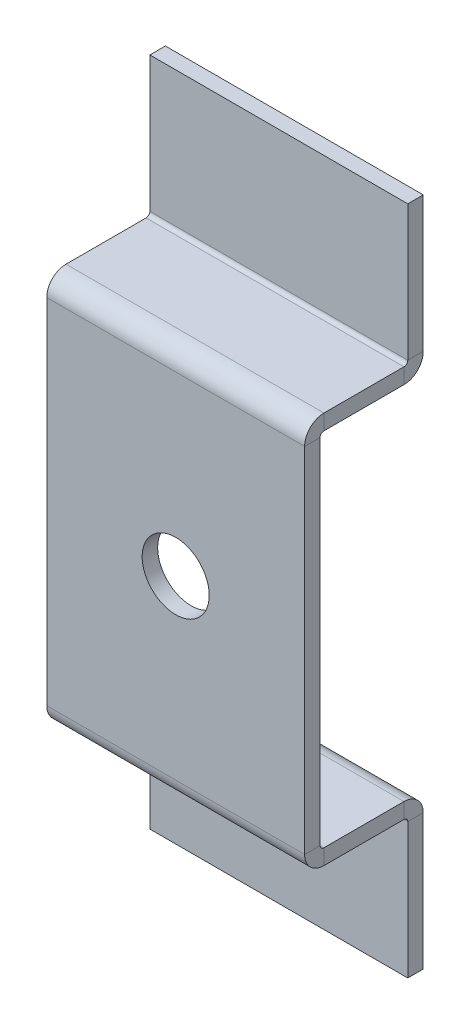
SolidWorks part; units mm, degrees
note: The reader was unsure of these and kept them because the rebuilt part matched: flange length of "边线-法兰1", "边线-法兰2".
ref_plane "前视基准面" through (0, 0, 0) normal (0, 0, 1) x (1, 0, 0)
ref_plane "上视基准面" through (0, 0, 0) normal (0, 1, 0) x (1, 0, 0)
ref_plane "右视基准面" through (0, 0, 0) normal (1, 0, 0) x (0, 0, -1)
other "Configuration Table"
sketch "草图1" plane through (0, 0, 0) normal (0, 0, 1) x (1, 0, 0)
  line L1 (0, 0) -> (50, 0)
  line L2 (0, 0) -> (0, 70)
  line L3 (0, 70) -> (50, 70)
  line L4 (50, 0) -> (50, 70)
  dimension "D1" = 70
  dimension "D2" = 50
base flange "基体-法兰1" sketch "草图1" thickness 3 reverse thickness direction no parameters "D1"=0.7366
edge flange "边线-法兰1" sketch "草图10" flange profiles "草图10", "草图11" flange angle 90 flange length 20 flange position material outside bend radius 0.7366 thickness 3 relief rectangular parameters "D6"=10, "D8"=1
sketch "草图10" plane through (0, 70, -3) normal (0, -1, 0) x (-1, 0, 0)
  line L2 (-50, 0) -> (-50, 17)
  line L3 (-50, 17) -> (0, 17)
  line L4 (0, 17) -> (0, 0)
  line L5 (0, 0) -> (-50, 0) construction
  line L6 (0, 0) -> (-50, 0)
sketch "草图11" plane through (0, 0, -3) normal (0, 1, 0) x (1, 0, 0)
  line L0 (50, 0) -> (0, 0) construction
  line L1 (50, 0) -> (0, 0)
  line L2 (50, 0) -> (50, 17)
  line L3 (50, 17) -> (0, 17)
  line L4 (0, 17) -> (0, 0)
bend "边线折弯1" bend radius 0.7366 bend angle 90 parameters "D5"=1
bend "边线折弯2" bend radius 0.7366 bend angle 90 parameters "D5"=2
edge flange "边线-法兰2" sketch "草图16" flange profiles "草图16", "草图17" flange angle 90 flange length 30 flange position material outside bend radius 0.7366 thickness 3 relief rectangular parameters "D6"=10, "D8"=1
sketch "草图16" plane through (0, -3, -20) normal (0, 0, -1) x (1, 0, 0)
  line L2 (0, 0) -> (0, 27)
  line L3 (0, 27) -> (50, 27)
  line L4 (50, 27) -> (50, 0)
  line L7 (50, 0) -> (0, 0) construction
  line L8 (50, 0) -> (0, 0)
sketch "草图17" plane through (0, 73, -20) normal (0, 0, -1) x (-1, 0, 0)
  line L0 (0, 0) -> (-50, 0) construction
  line L1 (0, 0) -> (-50, 0)
  line L2 (-50, 0) -> (-50, 27)
  line L3 (-50, 27) -> (0, 27)
  line L4 (0, 27) -> (0, 0)
bend "边线折弯3" bend radius 0.7366 bend angle 90 parameters "D5"=3
bend "边线折弯4" bend radius 0.7366 bend angle 90 parameters "D5"=4
sketch "草图18" plane through (0, 0, 0) normal (0, 0, 1) x (1, 0, 0)
  line L7 (50, -30) -> (0, -30) construction
  line L8 (50, 0.7366) -> (50, 69.2634) construction
  circle A0 centre (25, 35) radius 6.5
  dimension "D5" = 13
  dimension "D3" = 65
  dimension "D4" = 25
extrude "切除-拉伸1" cut sketch "草图18" against normal through all normal cut yes
sketch "折弯-线1" plane through (0, 0, 0) normal (0, 1, 0) x (1, 0, 0)
sketch "边界框1" plane through (0, 0, 0) normal (0, 1, 0) x (1, 0, 0)
sheet metal parameters "钣金6" thickness 3 parameters "D1"=0.7366
flat pattern "平板型式6" [suppressed]
sketch "折弯-线2" plane through (0, 0, 0) normal (0, 1, 0) x (1, 0, 0)
sketch "边界框2" [suppressed] plane through (0, 0, 0) normal (0, 1, 0) x (1, 0, 0)
sheet metal parameters "钣金7" thickness 3 parameters "D1"=0.7366
flat pattern "平板型式6" [suppressed]
sketch "折弯-线2" plane through (0, 0, 0) normal (0, 1, 0) x (1, 0, 0)
sketch "边界框2" [suppressed] plane through (0, 0, 0) normal (0, 1, 0) x (1, 0, 0)
bend of the flat pattern "展平-<边线折弯1>1"
bend of the flat pattern "展平-<边线折弯2>1"
sheet metal parameters "钣金8" thickness 3 parameters "D1"=0.7366
flat pattern "平板型式6" [suppressed]
sketch "折弯-线2" plane through (0, 0, 0) normal (0, 1, 0) x (1, 0, 0)
sketch "边界框2" [suppressed] plane through (0, 0, 0) normal (0, 1, 0) x (1, 0, 0)
bend of the flat pattern "展平-<边线折弯1>1"
bend of the flat pattern "展平-<边线折弯2>1"
bend of the flat pattern "展平-<边线折弯3>1"
bend of the flat pattern "展平-<边线折弯4>1"
sheet metal parameters "钣金9" thickness 3 parameters "D1"=0.7366
flat pattern "平板型式6" [suppressed]
sketch "折弯-线2" plane through (0, 0, 0) normal (0, 1, 0) x (1, 0, 0)
sketch "边界框2" [suppressed] plane through (0, 0, 0) normal (0, 1, 0) x (1, 0, 0)
bend of the flat pattern "展平-<边线折弯1>1"
bend of the flat pattern "展平-<边线折弯2>1"
bend of the flat pattern "展平-<边线折弯3>1"
bend of the flat pattern "展平-<边线折弯4>1"
